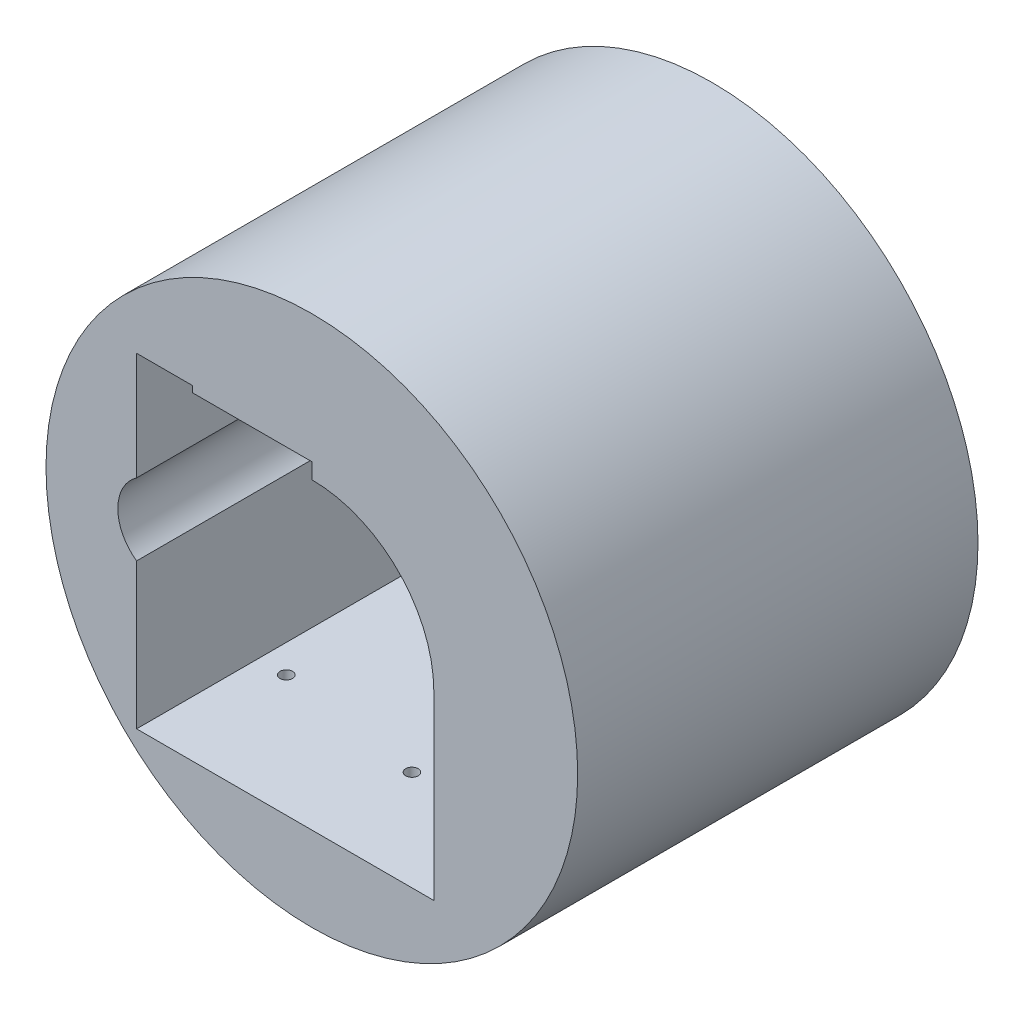
SolidWorks part; units mm, degrees
ref_plane "Front Plane" through (0, 0, 0) normal (0, 0, 1) x (1, 0, 0)
ref_plane "Top Plane" through (0, 0, 0) normal (0, 1, 0) x (1, 0, 0)
ref_plane "Right Plane" through (0, 0, 0) normal (1, 0, 0) x (0, 0, -1)
sketch "Sketch1" plane through (0, 0, -49.1287) normal (0, 0, -1) x (-1, 0, 0)
  line L0 (-13.8011, 15.8348) -> (-13.8011, -4)
  line L1 (-13.8011, 19.2554) -> (-13.8011, -4) construction
  line L2 (-13.8011, -4) -> (-61.3161, -4)
  line L3 (-61.3161, -4) -> (-61.3161, 25)
  line L4 (-13.8011, 34.1652) -> (-13.8011, 47)
  line L5 (-41.8161, 44.5) -> (-41.8161, 47)
  line L6 (-41.8161, 47) -> (-13.8011, 47)
  line L7 (-13.8011, 34.1652) -> (-13.8011, 30.7446)
  line L8 (-13.8011, 28) -> (-13.8011, 40.4952) construction
  line L9 (-13.8011, 15.8348) -> (-13.8011, 19.2554)
  arc A0 (-43.5455, 22.5486) -> (-44.7471, 25.6399) centre (-41.8161, 25) ccw construction
  arc A1 (-43.5455, 22.5486) -> (-44.7471, 25.6399) centre (-41.8161, 25) ccw construction
  circle A2 centre (-41.8161, 25) radius 42.5
  circle A3 centre (-17.8011, 25) radius 10 construction
  arc A4 (-22.9119, 29.7833) -> (-61.3161, 25) centre (-41.8161, 25) ccw construction
  arc A5 (-41.8161, 44.5) -> (-61.3161, 25) centre (-41.8161, 25) ccw
  arc A9 (-13.8011, 19.2554) -> (-13.8011, 30.7446) centre (-17.8011, 25) ccw
  dimension "D1" = 85
extrude "Boss-Extrude1" add sketch "Sketch1" against normal blind 64
ref_plane "Plane1" through (0, -17.5, 0) normal (0, -1, 0) x (-1, 0, 0)
sketch "Sketch2" plane through (0, -17.5, 0) normal (0, -1, 0) x (-1, 0, 0)
  circle A0 centre (-18.3011, 4.5578) radius 1 construction
  circle A1 centre (-18.3011, 32.5578) radius 1 construction
  circle A2 centre (-18.3011, 4.5578) radius 1
  circle A3 centre (-18.3011, 32.5578) radius 1
  circle A6 centre (-41.8161, 1.1287) radius 1 construction
  circle A7 centre (-41.8161, 1.1287) radius 1
extrude "Cut-Extrude1" cut sketch "Sketch2" against normal up to surface (13.5 mm away) up to face at (37.5586, -4, -17.1287)
sketch "Sketch3" plane through (0, -17.5, 0) normal (0, -1, 0) x (-1, 0, 0)
  circle A0 centre (-41.8161, 1.1287) radius 2.25
  circle A1 centre (-18.3011, 4.5578) radius 2.25
  circle A2 centre (-18.3011, 32.5578) radius 2.25
  dimension "D1" = 4.5
extrude "Cut-Extrude2" cut sketch "Sketch3" against normal blind 5
sketch "Sketch4" plane through (0, -17.5, 0) normal (0, -1, 0) x (-1, 0, 0)
  circle A0 centre (-18.3011, 4.5578) radius 2.25
  circle A1 centre (-18.3011, 32.5578) radius 2.25
extrude "Cut-Extrude3" cut sketch "Sketch4" against normal blind 12
sketch "Sketch5" plane through (0, 0, -49.1287) normal (0, 0, -1) x (-1, 0, 0)
  line L0 (-21.8011, 47) -> (-13.8011, 47)
  line L1 (-13.8011, 47) -> (-13.8011, 48)
  line L7 (-13.8011, 48) -> (-21.8011, 48)
  line L17 (-21.8011, 47) -> (-22.7487, 47)
  line L19 (-21.8011, 48) -> (-22.7487, 48)
  line L20 (-22.7487, 47) -> (-22.7487, 48)
extrude "Cut-Extrude4" cut sketch "Sketch5" against normal through all
